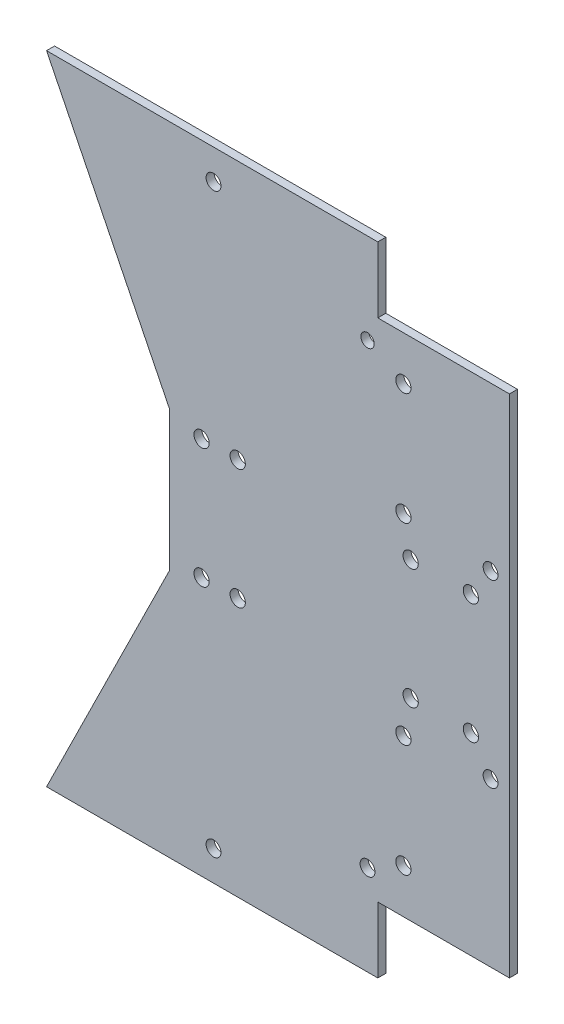
SolidWorks part; units mm, degrees
material "Thornel Mat VMA"
ref_plane "Front Plane" through (0, 0, 0) normal (0, 0, 1) x (1, 0, 0)
ref_plane "Top Plane" through (0, 0, 0) normal (0, 1, 0) x (1, 0, 0)
ref_plane "Right Plane" through (0, 0, 0) normal (1, 0, 0) x (0, 0, -1)
sketch "Sketch2" plane through (0, 0, 0) normal (0, 0, 1) x (-1, 0, 0)
  line L11 (-2.9301, 168.7083) -> (38.7094, 168.7083)
  line L12 (-2.9301, 8.6883) -> (38.7094, 8.6883)
  line L13 (38.7094, -12.1397) -> (38.7094, 8.6883)
  line L14 (143.4971, -12.1397) -> (38.7094, -12.1397)
  line L15 (38.7094, 189.5363) -> (38.7094, 168.7083)
  line L16 (143.4971, 189.5363) -> (38.7094, 189.5363)
  line L17 (104.6174, 110.8598) -> (143.4971, 189.5363)
  line L18 (104.6174, 66.5368) -> (143.4971, -12.1397)
  line L19 (104.6174, 66.5368) -> (72.8674, 66.5368)
  line L20 (72.8674, 66.5368) -> (72.8674, 110.8598)
  line L21 (104.6174, 110.8598) -> (72.8674, 110.8598)
  line L22 (-2.9301, 168.7083) -> (-2.9301, 8.6883)
  line L23 (41.9566, 19.6103) -> (41.9566, 13.2603) construction
  circle A0 centre (41.9566, 160.9613) radius 2.3495
  circle A1 centre (90.6739, 180.0113) radius 2.3495
  circle A2 centre (90.6739, -2.6147) radius 2.3495
  circle A3 centre (3.0351, 117.2098) radius 2.3495
  circle A4 centre (3.0351, 60.1868) radius 2.3495
  circle A5 centre (41.9566, 16.4353) radius 2.0955
  point P36 (41.9566, 16.4353)
  dimension "D3" = 4.699
  dimension "D7" = 31.75
  dimension "D8" = 41.6395
  dimension "D9" = 20.828
  dimension "D10" = 160.02
  dimension "D11" = 20.828
  dimension "D12" = 41.6395
  dimension "D13" = 104.7876
  dimension "D14" = 116.297
  dimension "D15" = 116.297
  dimension "D16" = 44.323
  dimension "D17" = 26.297
  dimension "D18" = 9.525
  dimension "D19" = 28.575
  dimension "D20" = 7.747
  dimension "D21" = 51.9645
  dimension "D22" = 51.4985
  dimension "D23" = 5.9651
  dimension "D24" = 51.4985
  dimension "D25" = 5.9651
  dimension "D26" = 7.747
  dimension "D27" = 3.2471
  dimension "D28" = 9.525
  dimension "D29" = 51.9645
extrude "Boss-Extrude1" add sketch "Sketch2" along normal blind 2.54
sketch "Sketch3" plane through (0, 0, 2.54) normal (0, 0, 1) x (1, 0, 0)
  line L1 (-104.6174, -66.5368) -> (-72.8674, -66.5368)
  line L2 (-104.6174, -66.5368) -> (-104.6174, -110.8598)
  line L3 (-104.6174, -110.8598) -> (-72.8674, -110.8598)
  line L4 (-72.8674, -66.5368) -> (-72.8674, -110.8598)
extrude "Boss-Extrude2" add sketch "Sketch3" against normal up to surface (2.54 mm away) up to face at (-65.9118, -88.6983, 0)
sketch "Sketch4" plane through (0, 0, 2.54) normal (0, 0, 1) x (1, 0, 0)
  line L0 (-104.6174, -66.5368) -> (-104.6174, -72.8868)
  line L1 (-104.6174, -66.5368) -> (-104.6174, -110.8598) construction
  line L2 (-104.6174, -69.7118) -> (2.9301, -69.7118) construction
  line L3 (2.9301, -168.7083) -> (2.9301, -8.6883) construction
  line L4 (-104.6174, -88.6983) -> (2.9301, -88.6983) construction
  line L5 (-104.6174, -107.6848) -> (2.9301, -107.6848) construction
  line L6 (-104.6174, -110.8598) -> (-104.6174, -104.5098)
  circle A0 centre (-94.4574, -69.7118) radius 2.413
  circle A1 centre (-83.0274, -69.7118) radius 2.413
  circle A2 centre (-28.3119, -69.7118) radius 2.413
  circle A3 centre (-9.2619, -69.7118) radius 2.413
  circle A4 centre (-9.2619, -107.6848) radius 2.413
  circle A5 centre (-28.3119, -107.6848) radius 2.413
  circle A6 centre (-83.0274, -107.6848) radius 2.413
  circle A7 centre (-94.4574, -107.6848) radius 2.413
  dimension "D2" = 10.16
  dimension "D4" = 4.826
  dimension "D5" = 4.826
  dimension "D8" = 4.826
  dimension "D9" = 4.826
  dimension "D1" = 3.175
  dimension "D3" = 11.43
  dimension "D6" = 19.05
  dimension "D7" = 12.192
extrude "Cut-Extrude1" cut sketch "Sketch4" against normal through all contours A0 | A1 | A2 | A3 | A4 | A5 | A6 | A7
sketch "Sketch5" plane through (0, 0, 2.54) normal (0, 0, 1) x (1, 0, 0)
  circle A0 centre (-30.6064, -58.2818) radius 2.413
  point P5 (0, 0)
  point P6 (0, 0)
  dimension "D1" = 4.826
sketch "Sketch6" plane through (0, 0, 2.54) normal (0, 0, 1) x (1, 0, 0)
  circle A0 centre (-30.6064, -22.7218) radius 2.413
  dimension "D1" = 4.826
extrude "Cut-Extrude2" cut sketch "Sketch5" against normal through all
extrude "Cut-Extrude3" cut sketch "Sketch6" against normal through all
sketch "Sketch7" plane through (0, 0, 2.54) normal (0, 0, 1) x (1, 0, 0)
  circle A0 centre (-30.6064, -154.6748) radius 2.413
  circle A1 centre (-30.6064, -119.1148) radius 2.413
  dimension "D1" = 4.826
  dimension "D2" = 4.826
extrude "Cut-Extrude4" cut sketch "Sketch7" against normal through all
